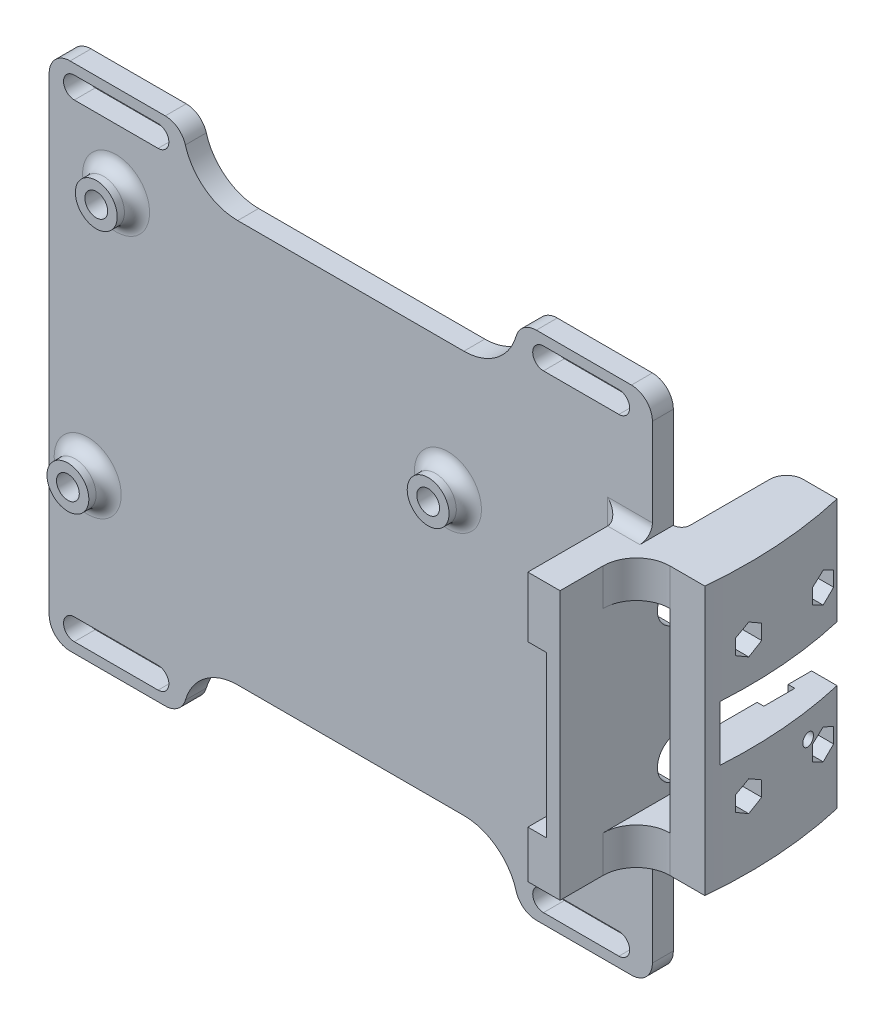
SolidWorks part; units mm, degrees
ref_plane "Front Plane" through (0, 0, 0) normal (0, 0, 1) x (1, 0, 0)
ref_plane "Top Plane" through (0, 0, 0) normal (0, 1, 0) x (1, 0, 0)
ref_plane "Right Plane" through (0, 0, 0) normal (1, 0, 0) x (0, 0, -1)
sketch "Sketch1" plane through (0, 0, 0) normal (0, 0, 1) x (1, 0, 0)
  line L1 (52.705, 30.48) -> (-52.705, 30.48)
  line L2 (52.705, 30.48) -> (52.705, -30.48)
  line L3 (52.705, -30.48) -> (-52.705, -30.48)
  line L4 (-52.705, 30.48) -> (-52.705, -30.48)
  line L5 (52.705, 30.48) -> (-52.705, -30.48) construction
  line L6 (52.705, -30.48) -> (-52.705, 30.48) construction
  point P0 (0, 0)
  dimension "D1" = 105.41
  dimension "D2" = 60.96
extrude "Boss-Extrude1" add sketch "Sketch1" along normal blind 3.175
sketch "Sketch20" plane through (0, 30.48, 0) normal (0, 1, 0) x (1, 0, 0)
  line L0 (52.705, -3.175) -> (-52.705, -3.175) construction
  line L1 (-38.735, -3.175) -> (-18.415, -3.175)
  line L2 (-38.735, -3.175) -> (-38.735, 0)
  line L3 (-38.735, 0) -> (-18.415, 0)
  line L4 (-18.415, -3.175) -> (-18.415, 0)
  line L5 (52.705, 0) -> (-52.705, 0) construction
  line L6 (-52.705, -3.175) -> (-52.705, 0) construction
  line L8 (52.705, 0) -> (32.385, 0)
  line L9 (52.705, 0) -> (52.705, -3.175)
  line L10 (52.705, -3.175) -> (32.385, -3.175)
  line L11 (32.385, 0) -> (32.385, -3.175)
  dimension "D1" = 13.97
  dimension "D2" = 20.32
  dimension "D3" = 20.32
  dimension "D4" = 50.8
extrude "Mounting Tab" add sketch "Sketch20" along normal blind 8.255
mirror "Mirror1" about plane through (0, 0, 0) normal (0, 1, 0) of "Mounting Tab"
fillet "Fillet10" radius 8.255 6 edges at (32.385, -30.48, 1.5875) (32.385, 30.48, 1.5875)
sketch "Sketch3" plane through (0, 0, 3.175) normal (0, 0, 1) x (1, 0, 0)
  line L0 (0, 0) -> (119.7861, 0) construction
  line L1 (47.818, 20.32) -> (52.705, 20.32)
  line L2 (47.818, 20.32) -> (47.818, -20.32)
  line L3 (47.818, -20.32) -> (52.705, -20.32)
  line L4 (52.705, 20.32) -> (52.705, -20.32)
  line L5 (52.705, -38.735) -> (52.705, 38.735) construction
  dimension "D1" = 40.64
  dimension "D3" = 4.887
extrude "Boss-Extrude2" add sketch "Sketch3" along normal blind 13.9954
fillet "Fillet2" radius 1.905 3 edges at (47.818, 0, 3.175)
sketch "Sketch4" plane through (47.818, 0, 0) normal (-1, 0, 0) x (0, 0, 1)
  line L1 (17.1704, 11.176) -> (11.5316, 11.176)
  line L2 (17.1704, 11.176) -> (17.1704, -13.1572)
  line L3 (17.1704, -13.1572) -> (11.5316, -13.1572)
  line L4 (11.5316, 11.176) -> (11.5316, -13.1572)
  line L5 (17.1704, 20.32) -> (5.08, 20.32) construction
  line L7 (3.175, -22.225) -> (3.175, 22.225) construction
  line L8 (17.1704, 20.32) -> (17.1704, -20.32) construction
  dimension "D1" = 8.3566
  dimension "D2" = 24.3332
  dimension "D4" = 9.144
extrude "SD card Slot" cut sketch "Sketch4" against normal blind 2.794
sketch "Sketch6" plane through (0, 0, 3.175) normal (0, 0, 1) x (1, 0, 0)
  circle A0 centre (-32.897, -14.3874) radius 3.175
  circle A1 centre (21.713, 11.0126) radius 3.175
  circle A2 centre (21.713, 11.0126) radius 1.45 construction
  circle A3 centre (-28.5917, 24.8556) radius 3.175
  circle A4 centre (-28.5917, 24.8556) radius 1.45 construction
  dimension "D1" = 6.35
  dimension "D3" = 54.61
  dimension "D4" = 25.4
sketch "Sketch5" plane through (0, 0, 0) normal (0, 0, -1) x (-1, 0, 0)
  line L0 (52.705, -30.48) -> (46.99, -30.48) construction
  line L1 (22.225, 35.56) -> (34.925, 35.56) construction
  line L2 (22.225, 37.1919) -> (34.925, 37.1919)
  line L3 (-52.705, -30.48) -> (-52.705, -20.32) construction
  line L4 (-47.625, -35.56) -> (-36.195, -35.56) construction
  line L5 (-47.625, -33.9281) -> (-36.195, -33.9281)
  line L6 (-47.625, -37.192) -> (-36.195, -37.192)
  line L13 (-47.625, 35.56) -> (-36.195, 35.56) construction
  line L14 (-47.625, 37.1919) -> (-36.195, 37.1919)
  line L15 (-47.625, 33.928) -> (-36.195, 33.928)
  line L16 (22.225, 33.928) -> (34.925, 33.928)
  line L17 (-11.4366, 0) -> (63.2813, 0) construction
  line L18 (22.225, -35.56) -> (34.925, -35.56) construction
  line L19 (22.225, -37.1919) -> (34.925, -37.1919)
  line L20 (22.225, -33.928) -> (34.925, -33.928)
  line L192 (28.575, -35.56) -> (40.005, -35.56) construction
  line L193 (28.575, -33.9281) -> (40.005, -33.9281)
  line L194 (28.575, -37.192) -> (40.005, -37.192)
  line L195 (28.575, 35.56) -> (40.005, 35.56) construction
  line L196 (28.575, 37.1919) -> (40.005, 37.1919)
  line L197 (28.575, 33.928) -> (40.005, 33.928)
  line L198 (28.575, -35.56) -> (40.005, -35.56) construction
  line L199 (28.575, -33.9281) -> (40.005, -33.9281)
  line L200 (28.575, -37.192) -> (40.005, -37.192)
  line L201 (28.575, 35.56) -> (40.005, 35.56) construction
  line L202 (28.575, 37.1919) -> (40.005, 37.1919)
  line L203 (28.575, 33.928) -> (40.005, 33.928)
  arc A4 (-47.625, -33.9281) -> (-47.625, -37.192) centre (-47.625, -35.56) ccw
  arc A5 (-36.195, -37.192) -> (-36.195, -33.9281) centre (-36.195, -35.56) ccw
  arc A6 (-47.625, 37.1919) -> (-47.625, 33.928) centre (-47.625, 35.56) ccw
  arc A7 (-36.195, 33.928) -> (-36.195, 37.1919) centre (-36.195, 35.56) ccw
  arc A8 (22.225, 37.1919) -> (22.225, 33.928) centre (22.225, 35.56) ccw
  arc A9 (34.925, 33.928) -> (34.925, 37.1919) centre (34.925, 35.56) ccw
  arc A10 (22.225, -37.1919) -> (22.225, -33.928) centre (22.225, -35.56) cw
  arc A11 (34.925, -33.928) -> (34.925, -37.1919) centre (34.925, -35.56) cw
  arc A130 (28.575, -33.9281) -> (28.575, -37.192) centre (28.575, -35.56) ccw
  arc A131 (40.005, -37.192) -> (40.005, -33.9281) centre (40.005, -35.56) ccw
  arc A132 (28.575, 37.1919) -> (28.575, 33.928) centre (28.575, 35.56) ccw
  arc A133 (40.005, 33.928) -> (40.005, 37.1919) centre (40.005, 35.56) ccw
  point P3 (28.575, 35.56)
  point P12 (-41.91, -35.56)
  point P22 (34.29, -25.4)
  point P28 (-41.91, 35.56)
  point P44 (28.575, -35.56)
  point P51 (34.29, 25.4)
  point P58 (34.29, -25.4)
  point P65 (34.29, 25.4)
  point P72 (34.29, -25.4)
  point P79 (34.29, 25.4)
  point P86 (34.29, -25.4)
  point P93 (34.29, 25.4)
  point P100 (34.29, -25.4)
  point P107 (34.29, 25.4)
  point P114 (34.29, -25.4)
  point P121 (34.29, 25.4)
  point P128 (34.29, -25.4)
  point P135 (34.29, 25.4)
  point P142 (34.29, -25.4)
  point P149 (34.29, 25.4)
  point P156 (34.29, -25.4)
  point P163 (34.29, 25.4)
  point P170 (34.29, -25.4)
  point P177 (34.29, 25.4)
  point P184 (34.29, -25.4)
  point P191 (34.29, 25.4)
  point P198 (34.29, -25.4)
  point P205 (34.29, 25.4)
  point P212 (34.29, -25.4)
  point P219 (34.29, 25.4)
  point P226 (34.29, -25.4)
  point P233 (34.29, 25.4)
  point P240 (34.29, -25.4)
  point P247 (34.29, 25.4)
  point P254 (34.29, -25.4)
  point P261 (34.29, 25.4)
  point P268 (34.29, -25.4)
  point P275 (34.29, 25.4)
  point P282 (34.29, -25.4)
  point P289 (34.29, 25.4)
  point P296 (34.29, -35.56)
  point P303 (34.29, 35.56)
  point P310 (34.29, -35.56)
  point P317 (34.29, 35.56)
  point P324 (34.29, -35.56)
  point P331 (34.29, 35.56)
  point P338 (34.29, -35.56)
  point P345 (34.29, 35.56)
  point P352 (34.29, -35.56)
  point P359 (34.29, 35.56)
  point P366 (34.29, -35.56)
  point P373 (34.29, 35.56)
  point P380 (34.29, -35.56)
  point P387 (34.29, 35.56)
  point P394 (34.29, -35.56)
  point P401 (34.29, 35.56)
  point P408 (34.29, -35.56)
  point P415 (34.29, 35.56)
  point P422 (34.29, -35.56)
  point P429 (34.29, 35.56)
  point P436 (34.29, -35.56)
  point P443 (34.29, 35.56)
  point P450 (34.29, -35.56)
  point P457 (34.29, 35.56)
  point P464 (34.29, -35.56)
  point P471 (34.29, 35.56)
  dimension "D1" = 1.632
  dimension "D6" = 2
  dimension "D8" = 1.6319
  dimension "D11" = 58.42
  dimension "D4" = 5.08
  dimension "D5" = 5.08
  dimension "D2" = 11.43
  dimension "D7" = 0
  dimension "D9" = 71.12
  dimension "D10" = 12.7
  dimension "D3" = 2
extrude "Mounting slots" cut sketch "Sketch5" against normal up to next
sketch "Sketch8" plane through (52.705, 0, 0) normal (1, 0, 0) x (0, 0, -1)
  line L1 (-11.938, -20.32) -> (15.875, -20.32)
  line L2 (-11.938, -20.32) -> (-11.938, 20.32)
  line L3 (-11.938, 20.32) -> (15.875, 20.32)
  line L4 (15.875, -20.32) -> (15.875, 20.32)
  line L6 (-9.1929, 0) -> (7.5537, 0) construction
  line L7 (0.762, 4.5369) -> (0.762, -4.1382) construction
  line L8 (0, -38.735) -> (0, 38.735) construction
  line L9 (-17.1704, 20.32) -> (-5.08, 20.32) construction
  line L11 (-17.1704, -20.32) -> (-5.08, -20.32) construction
  dimension "D1" = 11.938
  dimension "D2" = 0.762
  dimension "D3" = 15.875
extrude "Camera Mount" add sketch "Sketch8" along normal blind 38.1
sketch "Sketch9" plane through (0, 0, 3.175) normal (0, 0, 1) x (1, 0, 0)
  line L0 (-53.0586, 25.8373) -> (58.7014, -24.9627) construction
  line L1 (58.7014, 25.8373) -> (-53.0586, -24.9627) construction
  line L2 (58.7014, 25.8373) -> (-53.0586, 25.8373) construction
  line L3 (58.7014, 25.8373) -> (58.7014, -24.9627) construction
  line L4 (58.7014, -24.9627) -> (-53.0586, -24.9627) construction
  line L5 (-53.0586, 25.8373) -> (-53.0586, -24.9627) construction
  line L6 (0, 0) -> (-38.1087, 0) construction
  line L7 (-63.8536, -101.1627) -> (69.4964, -101.1627)
  line L8 (-63.8536, -101.1627) -> (-63.8536, 102.0373)
  line L9 (-63.8536, 102.0373) -> (69.4964, 102.0373)
  line L10 (69.4964, -101.1627) -> (69.4964, 102.0373)
  line L11 (-63.8536, -101.1627) -> (69.4964, 102.0373) construction
  line L12 (-63.8536, 102.0373) -> (69.4964, -101.1627) construction
  line L13 (52.705, 14.732) -> (57.785, 14.732)
  line L14 (52.705, 14.732) -> (52.705, -14.732)
  line L15 (52.705, -14.732) -> (57.785, -14.732)
  line L16 (57.785, 14.732) -> (57.785, -14.732)
  line L17 (52.705, 20.32) -> (52.705, 38.735) construction
  line L18 (24.13, 30.48) -> (-10.16, 30.48) construction
  arc A0 (36.195, 37.1919) -> (36.195, 33.928) centre (36.195, 35.56) ccw construction
  point P0 (2.8214, 0.4373)
  dimension "D7" = 89.2536
  dimension "D1" = 111.76
  dimension "D2" = 50.8
  dimension "D3" = 133.35
  dimension "D4" = 203.2
  dimension "D5" = 5.08
  dimension "D6" = 29.464
  dimension "D8" = 4.6427
sketch "Sketch10" plane through (0, 30.48, 0) normal (0, 1, 0) x (1, 0, 0)
  line L2 (0, -1.8666) -> (0, 5.5247) construction
  line L3 (24.13, 0) -> (-10.16, 0) construction
  line L4 (-124.1786, 120.847) -> (129.8214, 120.847)
  line L5 (-124.1786, 120.847) -> (-124.1786, -133.153)
  line L6 (-124.1786, -133.153) -> (129.8214, -133.153)
  line L7 (129.8214, 120.847) -> (129.8214, -133.153)
  circle A0 centre (-3.302, 0.8001) radius 66.675
  dimension "D2" = 133.35
  dimension "D1" = 0.8001
  dimension "D3" = 254
  dimension "D4" = 254
  dimension "D5" = 3.302
extrude "Cut-Extrude7" cut sketch "Sketch10" against normal through all and the other way through all
extrude "Cut-Extrude8" cut sketch "Sketch9" against normal through all and the other way through all from offset 4.064 contours L16 L15 L14 L13 offset against normal yes
sketch "Sketch11" plane through (57.785, 0, 0) normal (-1, 0, 0) x (0, 0, 1)
  line L0 (-0.762, -33.0757) -> (-0.762, 43.0894) construction
  line L1 (-15.875, -20.32) -> (-15.875, 20.32) construction
  line L2 (23.6947, 0) -> (-23.921, 0) construction
  line L4 (0, -38.735) -> (0, -20.32) construction
  line L5 (3.429, 4.191) -> (-18.415, 4.191)
  line L6 (3.429, 4.191) -> (3.429, -4.191)
  line L7 (3.429, -4.191) -> (-18.415, -4.191)
  line L8 (-18.415, 4.191) -> (-18.415, -4.191)
  line L12 (-15.875, -14.732) -> (11.938, -14.732) construction
  line L13 (-15.875, 14.732) -> (11.938, 14.732) construction
  circle A0 centre (-0.762, -10.287) radius 0.3175
  circle A1 centre (-0.762, 10.287) radius 0.3175
  circle A2 centre (-13.208, 10.287) radius 0.3175
  circle A3 centre (-13.208, -10.287) radius 0.3175
  point P8 (-0.762, 0)
  dimension "D5" = 0.635
  dimension "D6" = 20.574
  dimension "D2" = 0.635
  dimension "D1" = 0.762
  dimension "D3" = 4.191
  dimension "D4" = 8.382
  dimension "D7" = 2
  dimension "D8" = 2.54
extrude "Camera holes" cut sketch "Sketch11" against normal through all
sketch "Sketch36" plane through (57.785, 0, 0) normal (-1, 0, 0) x (0, 0, 1)
  line L1 (-7.62, -4.191) -> (-12.319, -4.191)
  line L2 (-7.62, -4.191) -> (-7.62, -9.271)
  line L3 (-7.62, -9.271) -> (-12.319, -9.271)
  line L4 (-12.319, -4.191) -> (-12.319, -9.271)
  line L6 (-15.875, -4.191) -> (3.429, -4.191) construction
  circle A1 centre (-13.208, -10.287) radius 0.3175 construction
  dimension "D1" = 0.889
  dimension "D2" = 1.016
  dimension "D3" = 4.699
extrude "Cut-Extrude19" cut sketch "Sketch36" against normal blind 1.016
extrude "Pi PCB standoff" add sketch "Sketch6" along normal blind 3
hole_wizard "#1 Clearance Hole1" positions "Sketch39" profile "Sketch38" hole size "#1" standard "ANSI Inch"
sketch "Sketch39" plane through (57.785, 0, 0) normal (-1, 0, 0) x (0, 0, 1)
  point P0 (-13.208, 10.287)
  point P3 (-0.762, 10.287)
  point P6 (-0.762, -10.287)
  point P9 (-13.208, -10.287)
sketch "Sketch38" plane through (57.785, 10.287, -13.208) normal (0, 1, 0) x (0, 0, 1)
  line L0 (0, 0) -> (0, 10.6181)
  line L1 (0, 10.6181) -> (1.0287, 10)
  line L2 (1.0287, 10) -> (1.0287, 0)
  line L5 (1.0287, 0) -> (0, 0)
  line L10 (0, 10.6181) -> (-1.0287, 10) construction
  line L11 (0, -6.35) -> (0, 107.95) construction
  dimension "Hole Dia." = 2.0574
  dimension "Hole Depth" = 10
  dimension "Drill Angle" = 118
sketch "Sketch40" plane through (57.785, 0, 0) normal (-1, 0, 0) x (0, 0, 1)
  line L1 (-13.208, 7.9956) -> (-11.2236, 9.1413)
  line L2 (-11.2236, 9.1413) -> (-11.2236, 11.4327)
  line L3 (-11.2236, 11.4327) -> (-13.208, 12.5784)
  line L4 (-13.208, 12.5784) -> (-15.1924, 11.4327)
  line L5 (-15.1924, 11.4327) -> (-15.1924, 9.1413)
  line L6 (-15.1924, 9.1413) -> (-13.208, 7.9956)
  line L7 (-0.762, 7.9956) -> (1.2224, 9.1413)
  line L8 (1.2224, 9.1413) -> (1.2224, 11.4327)
  line L9 (1.2224, 11.4327) -> (-0.762, 12.5784)
  line L10 (-0.762, 12.5784) -> (-2.7464, 11.4327)
  line L11 (-2.7464, 11.4327) -> (-2.7464, 9.1413)
  line L12 (-2.7464, 9.1413) -> (-0.762, 7.9956)
  line L13 (-0.762, -12.5784) -> (1.2224, -11.4327)
  line L14 (1.2224, -11.4327) -> (1.2224, -9.1413)
  line L15 (1.2224, -9.1413) -> (-0.762, -7.9956)
  line L16 (-0.762, -7.9956) -> (-2.7464, -9.1413)
  line L17 (-2.7464, -9.1413) -> (-2.7464, -11.4327)
  line L18 (-2.7464, -11.4327) -> (-0.762, -12.5784)
  line L19 (-13.208, -12.5784) -> (-11.2236, -11.4327)
  line L20 (-11.2236, -11.4327) -> (-11.2236, -9.1413)
  line L21 (-11.2236, -9.1413) -> (-13.208, -7.9956)
  line L22 (-13.208, -7.9956) -> (-15.1924, -9.1413)
  line L23 (-15.1924, -9.1413) -> (-15.1924, -11.4327)
  line L24 (-15.1924, -11.4327) -> (-13.208, -12.5784)
  circle A0 centre (-13.208, 10.287) radius 1.9844 construction
  circle A1 centre (-0.762, 10.287) radius 1.9844 construction
  circle A2 centre (-0.762, -10.287) radius 1.9844 construction
  circle A3 centre (-13.208, -10.287) radius 1.9844 construction
  dimension "D1" = 3.9688
  dimension "D2" = 3.9688
  dimension "D3" = 3.9688
  dimension "D4" = 3.9688
extrude "Cut-Extrude21" cut sketch "Sketch40" against normal up to next from offset 1.27 offset against normal yes
sketch "Sketch18" plane through (0, 0, 6.175) normal (0, 0, 1) x (1, 0, 0)
  circle A0 centre (21.713, 11.0126) radius 1.4605
  circle A1 centre (-32.897, -14.3874) radius 1.4605
  dimension "D1" = 2.921
  dimension "D2" = 2.921
extrude "Cut-Extrude13" cut sketch "Sketch18" against normal through all
sketch "Sketch29" plane through (0, 0, 0) normal (0, 0, -1) x (-1, 0, 0)
  line L1 (-18.9854, 11.0126) -> (-20.3492, 13.3748)
  line L2 (-20.3492, 13.3748) -> (-23.0769, 13.3748)
  line L3 (-23.0769, 13.3748) -> (-24.4407, 11.0126)
  line L4 (-24.4407, 11.0126) -> (-23.0769, 8.6504)
  line L5 (-23.0769, 8.6504) -> (-20.3492, 8.6504)
  line L6 (-20.3492, 8.6504) -> (-18.9854, 11.0126)
  line L7 (35.6246, -14.3874) -> (34.2608, -12.0252)
  line L8 (34.2608, -12.0252) -> (31.5331, -12.0252)
  line L9 (31.5331, -12.0252) -> (30.1693, -14.3874)
  line L10 (30.1693, -14.3874) -> (31.5331, -16.7496)
  line L11 (31.5331, -16.7496) -> (34.2608, -16.7496)
  line L12 (34.2608, -16.7496) -> (35.6246, -14.3874)
  line L13 (27.2278, 22.4934) -> (29.9555, 22.4934)
  line L14 (29.9555, 22.4934) -> (31.3193, 24.8556)
  line L15 (31.3193, 24.8556) -> (29.9555, 27.2178)
  line L16 (29.9555, 27.2178) -> (27.2278, 27.2178)
  line L17 (27.2278, 27.2178) -> (25.864, 24.8556)
  line L18 (25.864, 24.8556) -> (27.2278, 22.4934)
  circle A0 centre (-21.713, 11.0126) radius 2.3622 construction
  circle A1 centre (32.897, -14.3874) radius 2.3622 construction
  circle A2 centre (28.5917, 24.8556) radius 2.3622 construction
  circle A3 centre (28.5917, 24.8556) radius 3.175 construction
  dimension "D3" = 4.7244
extrude "hex holes" cut sketch "Sketch29" against normal blind 2.54
hole_wizard "#4 Clearance Hole1" positions "Sketch31" profile "Sketch30" hole size "#4" standard "ANSI Inch" end condition up to next
sketch "Sketch31" plane through (0, 0, 0) normal (0, 0, -1) x (-1, 0, 0)
  point P0 (32.897, -14.3874)
  point P3 (-21.713, 11.0126)
  point P6 (28.5917, 24.8556)
sketch "Sketch30" plane through (-32.897, -14.3874, 0) normal (1, 0, 0) x (0, 1, 0)
  line L0 (0, 0) -> (0, 17.1704)
  line L1 (0, 17.1704) -> (1.7272, 17.1704)
  line L2 (1.7272, 17.1704) -> (1.7272, 0)
  line L5 (1.7272, 0) -> (0, 0)
  line L11 (0, -6.35) -> (0, 107.95) construction
  dimension "Thru Hole Dia." = 3.4544
  dimension "Thru Hole Depth" = 17.1704
sketch "Sketch34" plane through (0, 20.32, 0) normal (0, 1, 0) x (1, 0, 0)
  line L1 (52.705, 0) -> (53.975, 0)
  line L2 (52.705, 0) -> (52.705, 28.5232)
  line L3 (52.705, 28.5232) -> (53.975, 28.5232)
  line L4 (53.975, 0) -> (53.975, 28.5232)
  dimension "D1" = 1.27
extrude "Cut-Extrude16" cut sketch "Sketch34" against normal through all
sketch "Sketch35" plane through (57.785, 0, 0) normal (-1, 0, 0) x (0, 0, 1)
  line L0 (-15.875, -20.32) -> (11.938, -20.32) construction
  line L1 (11.938, 20.32) -> (5.588, 20.32)
  line L2 (11.938, 20.32) -> (11.938, -20.32)
  line L3 (11.938, -20.32) -> (5.588, -20.32)
  line L4 (5.588, 20.32) -> (5.588, -20.32)
  line L5 (11.938, 20.32) -> (-15.875, 20.32) construction
  line L6 (11.938, 20.32) -> (11.938, -20.32) construction
  dimension "D1" = 6.35
extrude "Cut-Extrude17" cut sketch "Sketch35" against normal up to next from offset 5.08
fillet "Fillet9" radius 5.08 2 edges at (52.705, 17.526, 5.588) (52.705, -17.526, 5.588)
fillet "Fillet1" radius 1.905 3 edges at (-36.072, -14.3874, 3.175) (18.538, 11.0126, 3.175) (-31.7667, 24.8556, 3.175)
fillet "Fillet5" radius 1.27 2 edges at (53.975, -17.526, 0) (53.975, 17.526, 0)
fillet "Fillet6" radius 2.54 2 edges at (53.975, -17.526, -15.875) (53.975, 17.526, -15.875)
sketch "Sketch41" plane through (57.785, 0, 0) normal (-1, 0, 0) x (0, 0, 1)
  circle A0 centre (-0.762, 10.287) radius 3.175
  circle A1 centre (-0.762, -10.287) radius 3.175
  dimension "D1" = 6.35
  dimension "D2" = 6.35
extrude "Cut-Extrude23" cut sketch "Sketch41" along normal blind 12.7 from vertex starting at point (52.705, -14.732, 0)
sketch "Sketch43" plane through (0, 0, 3.175) normal (0, 0, 1) x (1, 0, 0)
  line L0 (0, 0) -> (-64.135, 0) construction
  line L1 (-64.135, -50.8) -> (-38.735, -50.8)
  line L2 (-64.135, -50.8) -> (-64.135, 50.8)
  line L3 (-64.135, 50.8) -> (-38.735, 50.8)
  line L4 (-38.735, -50.8) -> (-38.735, 50.8)
  line L9 (-52.705, 30.48) -> (-52.705, -30.48) construction
  dimension "D1" = 101.6
  dimension "D2" = 25.4
  dimension "D3" = 13.97
extrude "Cut-Extrude24" cut sketch "Sketch43" against normal through all
sketch "Sketch42" plane through (0, 0, 11.5316) normal (0, 0, 1) x (1, 0, 0)
  line L0 (50.612, -0.9906) -> (46.9767, -0.9906) construction
  line L1 (50.612, -13.1572) -> (48.326, -13.1572)
  line L2 (50.612, -13.1572) -> (50.612, -10.6172)
  line L3 (50.612, -10.6172) -> (48.326, -10.6172)
  line L4 (48.326, -13.1572) -> (48.326, -10.6172)
  line L5 (50.612, 11.176) -> (50.612, -13.1572) construction
  line L6 (48.326, 11.176) -> (48.326, 8.636)
  line L7 (50.612, 8.636) -> (48.326, 8.636)
  line L8 (50.612, 11.176) -> (50.612, 8.636)
  line L9 (50.612, 11.176) -> (48.326, 11.176)
  dimension "D1" = 2.286
  dimension "D2" = 2.54
extrude "Boss-Extrude3" [suppressed] add sketch "Sketch42" along normal blind 4.191
fillet "Fillet13" [suppressed] radius 2.159
fillet "Fillet14" radius 3.175 8 edges at (-18.415, 38.735, 1.5875) (-38.735, 38.735, 1.5875) (-38.735, -38.735, 1.5875) (-18.415, -38.735, 1.5875) (32.385, 38.735, 1.5875) (52.705, 38.735, 1.5875) (52.705, -38.735, 1.5875) (32.385, -38.735, 1.5875)
fillet "Fillet15" [suppressed] radius 0.508
sketch "Sketch44" plane through (58.801, 0, 0) normal (-1, 0, 0) x (0, 0, 1)
  circle A0 centre (-10.4775, -8.0518) radius 0.9525
  circle A1 centre (-13.208, -10.287) radius 1.0287 construction
  dimension "D1" = 2.7305
  dimension "D3" = 1.905
  dimension "D2" = 2.2352
extrude "Cut-Extrude25" cut sketch "Sketch44" against normal through all
